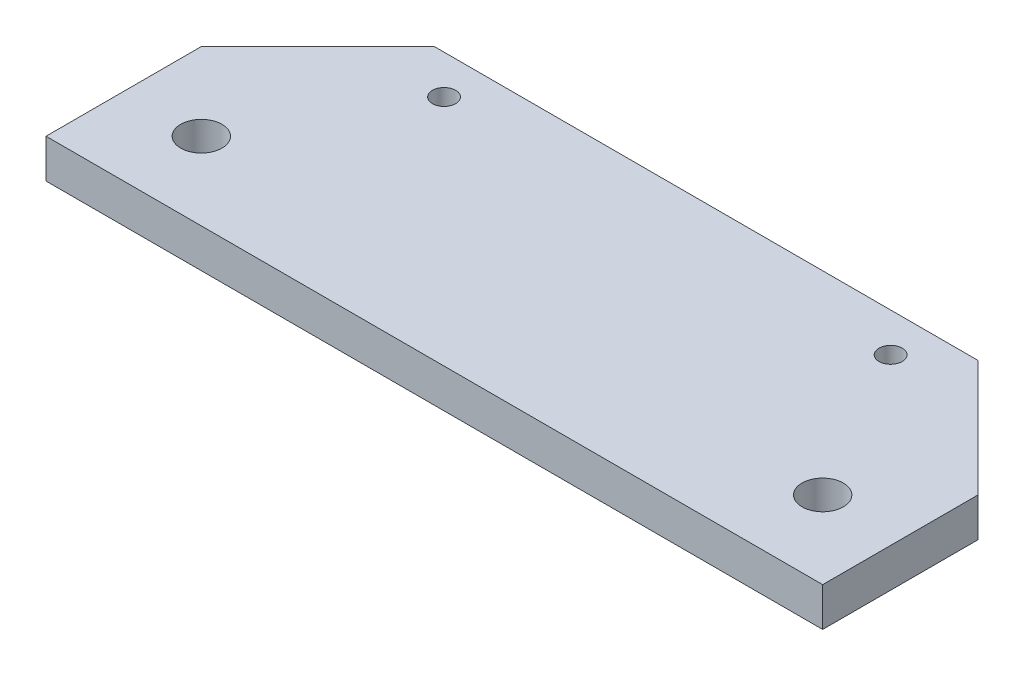
SolidWorks part; units mm, degrees
ref_plane "Front Plane" through (0, 0, 0) normal (0, 0, 1) x (1, 0, 0)
ref_plane "Top Plane" through (0, 0, 0) normal (0, 1, 0) x (1, 0, 0)
ref_plane "Right Plane" through (0, 0, 0) normal (1, 0, 0) x (0, 0, -1)
sketch "Sketch8" plane through (0, 0, 0) normal (0, 1, 0) x (1, 0, 0)
  line L0 (44.45, 0) -> (44.45, -12.7)
  line L1 (0, 0) -> (88.9, 0)
  line L2 (0, 0) -> (0, -12.7)
  line L3 (0, -12.7) -> (88.9, -12.7)
  line L4 (88.9, 0) -> (88.9, -12.7)
  line L5 (7.9375, -6.35) -> (80.9625, -6.35)
  line L6 (44.45, -12.7) -> (44.45, -31.75)
  line L7 (0, 0) -> (-19.05, -19.05)
  line L8 (-19.05, -19.05) -> (107.95, -19.05)
  line L9 (-19.05, -19.05) -> (-19.05, -44.45)
  line L10 (-19.05, -44.45) -> (107.95, -44.45)
  line L11 (107.95, -19.05) -> (107.95, -44.45)
  line L12 (-19.05, -19.05) -> (107.95, -44.45) construction
  line L13 (-19.05, -44.45) -> (107.95, -19.05) construction
  line L14 (88.9, 0) -> (107.95, -19.05)
  line L15 (95.25, -31.75) -> (-6.35, -31.75)
  point P10 (44.45, -6.35)
  point P15 (0, 0)
  point P23 (44.45, -31.75)
  dimension "D1" = 12.7
  dimension "D2" = 88.9
  dimension "D3" = 73.025
  dimension "D4" = 25.4
  dimension "D5" = 127
  dimension "D6" = 6.35
  dimension "D7" = 101.6
extrude "Boss-Extrude3" add sketch "Sketch8" along normal blind 6.35 contours L7 L8 L6 L3 L2 | L14 L4 L3 L6 L8 | L9 L8 L11 L10 | L2 L1 L4 L3 region at (11.0435, 0, 14.6326) region at (77.8565, 0, 14.6326)
hole_wizard "CBORE for #6 Socket Head Cap Screw1" positions "Sketch11" profile "Sketch12" counterbore size "#6" standard "ANSI Inch" end condition up to next
sketch "Sketch11" plane through (0, 0, 0) normal (0, -1, 0) x (-1, 0, 0)
  point P0 (-80.9625, -6.35)
  point P3 (-7.9375, -6.35)
sketch "Sketch12" plane through (80.9625, 0, 6.35) normal (1, 0, 0) x (0, 0, -1)
  line L0 (0, 0) -> (0, 6.35)
  line L1 (0, 6.35) -> (1.8986, 6.35)
  line L3 (1.8986, 6.35) -> (1.8986, 3.5052)
  line L4 (1.8986, 3.5052) -> (3.5725, 3.5052)
  line L5 (3.5725, 3.5052) -> (3.5725, 0)
  line L7 (3.5725, 0) -> (0, 0)
  line L11 (0, -6.35) -> (0, 107.95) construction
  dimension "Thru Hole Dia." = 3.7973
  dimension "Thru Hole Depth" = 6.35
  dimension "C'Bore Dia." = 7.145
  dimension "C'Bore Depth" = 3.5052
hole_wizard "1/4 Clearance Hole1" positions "Sketch13" profile "Sketch14" hole size "1/4" standard "ANSI Inch" end condition up to next
sketch "Sketch13" plane through (0, 6.35, 0) normal (0, 1, 0) x (1, 0, 0)
  point P0 (-6.35, -31.75)
  point P3 (95.25, -31.75)
sketch "Sketch14" plane through (-6.35, 6.35, 31.75) normal (1, 0, 0) x (0, 0, 1)
  line L0 (0, 0) -> (0, 6.35)
  line L1 (0, 6.35) -> (3.3782, 6.35)
  line L2 (3.3782, 6.35) -> (3.3782, 0)
  line L5 (3.3782, 0) -> (0, 0)
  line L11 (0, -6.35) -> (0, 107.95) construction
  dimension "Thru Hole Dia." = 6.7564
  dimension "Thru Hole Depth" = 6.35
